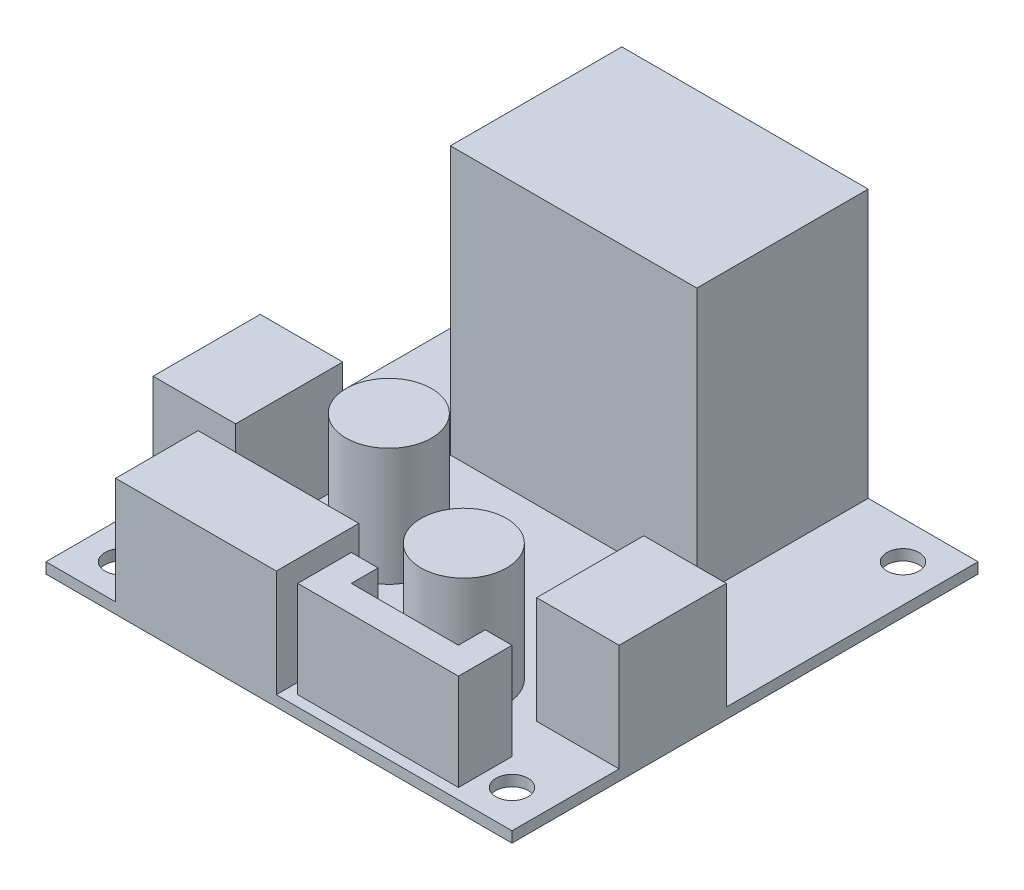
SolidWorks part; units mm, degrees
ref_plane "Front" through (0, 0, 0) normal (0, 0, 1) x (1, 0, 0)
ref_plane "Top" through (0, 0, 0) normal (0, 1, 0) x (1, 0, 0)
ref_plane "Right" through (0, 0, 0) normal (1, 0, 0) x (0, 0, -1)
sketch "Эскиз1" plane through (0, 0, 0) normal (0, 1, 0) x (1, 0, 0)
  line L1 (-21.75, 21.75) -> (21.75, 21.75)
  line L2 (-21.75, 21.75) -> (-21.75, -21.75)
  line L3 (-21.75, -21.75) -> (21.75, -21.75)
  line L4 (21.75, 21.75) -> (21.75, -21.75)
  line L5 (-21.75, 21.75) -> (21.75, -21.75) construction
  line L6 (-21.75, -21.75) -> (21.75, 21.75) construction
  point P0 (0, 0)
  dimension "D1" = 43.5
extrude "Бобышка-Вытянуть1" add sketch "Эскиз1" along normal blind 1
sketch "Эскиз2" plane through (0, 1, 0) normal (0, 1, 0) x (1, 0, 0)
  line L0 (21.75, 21.75) -> (-21.75, 21.75) construction
  line L1 (-11.5, 21.75) -> (11.5, 21.75)
  line L2 (-11.5, 21.75) -> (-11.5, 5.75)
  line L3 (-11.5, 5.75) -> (11.5, 5.75)
  line L4 (11.5, 21.75) -> (11.5, 5.75)
  line L5 (-21.75, 0) -> (21.75, 0) construction
  line L6 (-21.75, 21.75) -> (-21.75, -21.75) construction
  line L7 (21.75, -21.75) -> (21.75, 21.75) construction
  line L8 (0, -21.75) -> (0, 21.75) construction
  line L9 (-21.75, -21.75) -> (21.75, -21.75) construction
  line L10 (0.75, -20.75) -> (0.75, -15.75)
  line L11 (-21.75, -1.75) -> (-14.05, -1.75)
  line L12 (-21.75, -1.75) -> (-21.75, -11.75)
  line L13 (-21.75, -11.75) -> (-14.05, -11.75)
  line L14 (-14.05, -1.75) -> (-14.05, -11.75)
  line L15 (21.75, -1.75) -> (14.05, -1.75)
  line L16 (21.75, -1.75) -> (21.75, -11.75)
  line L17 (21.75, -11.75) -> (14.05, -11.75)
  line L18 (14.05, -1.75) -> (14.05, -11.75)
  line L19 (-15.25, -21.75) -> (-0.25, -21.75)
  line L20 (-15.25, -21.75) -> (-15.25, -14.05)
  line L21 (-15.25, -14.05) -> (-0.25, -14.05)
  line L22 (-0.25, -21.75) -> (-0.25, -14.05)
  line L23 (0.75, -15.75) -> (3.25, -15.75)
  line L24 (3.25, -15.75) -> (3.25, -18.25)
  line L25 (3.25, -18.25) -> (13.25, -18.25)
  line L26 (13.25, -18.25) -> (13.25, -15.75)
  line L27 (13.25, -15.75) -> (15.75, -15.75)
  line L28 (15.75, -15.75) -> (15.75, -20.75)
  line L29 (15.75, -20.75) -> (0.75, -20.75)
  circle A0 centre (18.25, 18.25) radius 1.5
  circle A1 centre (-18.25, 18.25) radius 1.5
  circle A2 centre (-18.25, -18.25) radius 1.5
  circle A3 centre (18.25, -18.25) radius 1.5
  circle A4 centre (7.25, -11.75) radius 4
  circle A5 centre (-6.75, -4.75) radius 4
  point P17 (0, 21.75)
  line M20 (21.75, -21.75) -> (21.75, 21.75)
  line M21 (21.75, 21.75) -> (-21.75, 21.75)
  line M22 (-21.75, 21.75) -> (-21.75, -21.75)
  line M23 (-21.75, -21.75) -> (21.75, -21.75)
  dimension "D3" = 3
  dimension "D18" = 8
  dimension "D1" = 23
  dimension "D2" = 16
  dimension "D4" = 3.5
  dimension "D5" = 3.5
  dimension "D6" = 2.5
  dimension "D7" = 5
  dimension "D8" = 2.5
  dimension "D9" = 15
  dimension "D10" = 1
  dimension "D11" = 6
  dimension "D12" = 7.7
  dimension "D13" = 1
  dimension "D14" = 15
  dimension "D15" = 10
  dimension "D16" = 7.7
  dimension "D17" = 10
  dimension "D19" = 4
  dimension "D20" = 4
  dimension "D21" = 17
  dimension "D22" = 15
extrude "Вырез-Вытянуть1" cut sketch "Эскиз2" against normal through all contours A1 | A0 | A3 | A2 region at (18.25, 1, -18.25) region at (-18.25, 1, -18.25) region at (-18.25, 1, 18.25) region at (18.25, 1, 18.25)
extrude "Бобышка-Вытянуть2" add sketch "Эскиз2<3>" along normal blind 25 contours L4 L2 L3 M21 region at (0, 1, -13.75)
sketch "Эскиз2<3>" plane through (0, 1, 0) normal (0, 1, 0) x (1, 0, 0) same geometry as "Эскиз2"
extrude "Бобышка-Вытянуть3" add sketch "Эскиз2<4>" along normal blind 10 contours L14 L11 L13 M22 | L15 L18 L17 M20 | L22 L21 L20 M23 region at (17.9, 1, 6.75) region at (-7.75, 1, 17.9) region at (-17.9, 1, 6.75)
sketch "Эскиз2<4>" plane through (0, 1, 0) normal (0, 1, 0) x (1, 0, 0) same geometry as "Эскиз2"
extrude "Бобышка-Вытянуть4" add sketch "Эскиз2<5>" along normal blind 9 contours L29 L28 L27 L26 L25 L24 L23 L10 region at (8.25, 1, 18.875)
sketch "Эскиз2<5>" plane through (0, 1, 0) normal (0, 1, 0) x (1, 0, 0) same geometry as "Эскиз2"
extrude "Бобышка-Вытянуть5" add sketch "Эскиз2<6>" along normal blind 11 contours A5 | A4 region at (7.25, 1, 11.75) region at (-6.75, 1, 4.75)
sketch "Эскиз2<6>" plane through (0, 1, 0) normal (0, 1, 0) x (1, 0, 0) same geometry as "Эскиз2"
